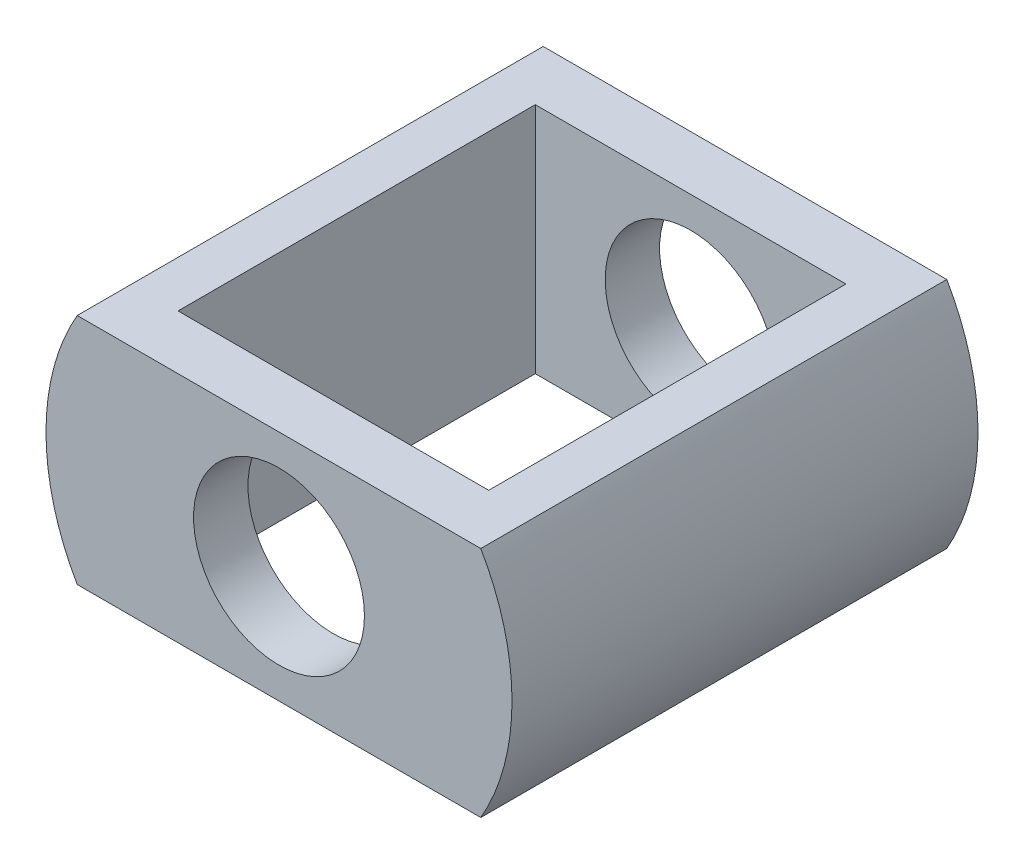
SolidWorks part; units mm, degrees
material "Aleación 1060"
ref_plane "Alzado" through (0, 0, 0) normal (1, 0, 0) x (0, 1, 0)
ref_plane "Planta" through (0, 0, 0) normal (0, 0, 1) x (0, 1, 0)
ref_plane "Vista lateral" through (0, 0, 0) normal (0, 1, 0) x (-1, 0, 0)
sketch "Croquis1" plane through (0, 0, 0) normal (0, 0, 1) x (0, 1, 0)
  line L0 (-30, 0) -> (30, 0) construction
  line L1 (-15, -25.9808) -> (-15, 25.9808)
  line L2 (0, 30) -> (0, -30) construction
  line L3 (15, -25.9808) -> (15, 25.9808)
  arc A0 (-15, -25.9808) -> (15, -25.9808) centre (0, 0) ccw
  arc A1 (15, 25.9808) -> (-15, 25.9808) centre (0, 0) ccw
  circle A2 centre (0, 0) radius 11
  dimension "D1" = 60
  dimension "D3" = 22
  dimension "D2" = 30
extrude "Saliente-Extruir1" add sketch "Croquis1" along normal blind 60
ref_plane "Plano1" through (0, 0, 30) normal (0, 0, 1) x (0, 1, 0)
sketch "Croquis2" plane through (0, 0, 30) normal (0, 0, 1) x (0, 1, 0)
  line L0 (-15, 25.9808) -> (-15, -25.9808) construction
  line L1 (15, -20) -> (-15, -20)
  line L2 (15, -20) -> (15, 20)
  line L3 (15, 20) -> (-15, 20)
  line L4 (-15, -20) -> (-15, 20)
  line L5 (0, 20) -> (0, -20) construction
  line L6 (15, 0) -> (-15, 0) construction
  point P0 (0, 0)
  dimension "D1" = 40
extrude "Cortar-Extruir1" cut sketch "Croquis2" against normal mid plane 46
